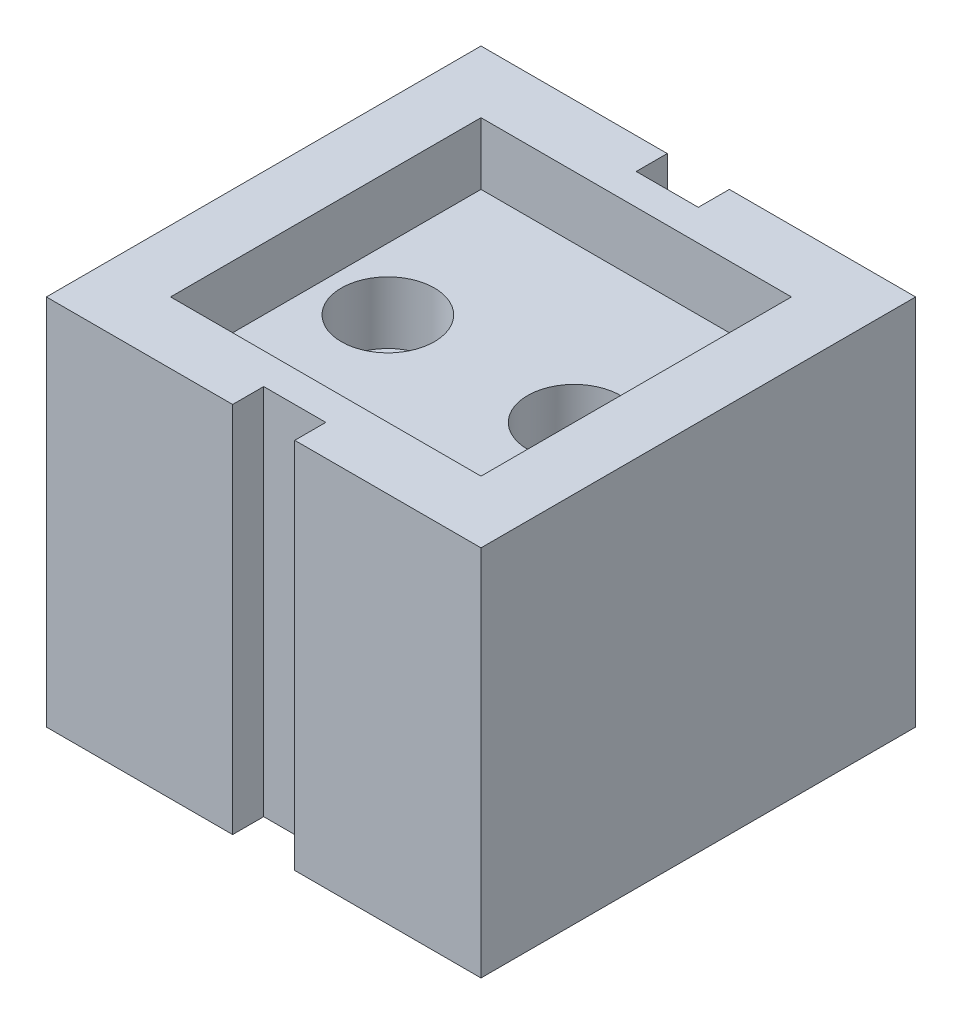
SolidWorks part; units mm, degrees
ref_plane "Front Plane" through (0, 0, 0) normal (0, 0, 1) x (1, 0, 0)
ref_plane "Top Plane" through (0, 0, 0) normal (0, 1, 0) x (1, 0, 0)
ref_plane "Right Plane" through (0, 0, 0) normal (1, 0, 0) x (0, 0, -1)
sketch "Sketch1" plane through (0, 0, 0) normal (0, 1, 0) x (1, 0, 0)
  line L1 (-3.5, -3.5) -> (3.5, -3.5)
  line L2 (-3.5, -3.5) -> (-3.5, 3.5)
  line L3 (-3.5, 3.5) -> (3.5, 3.5)
  line L4 (3.5, -3.5) -> (3.5, 3.5)
  line L5 (-3.5, -3.5) -> (3.5, 3.5) construction
  line L6 (-3.5, 3.5) -> (3.5, -3.5) construction
  point P0 (0, 0)
  dimension "D1" = 7
extrude "Boss-Extrude1" add sketch "Sketch1" along normal blind 6
sketch "Sketch2" plane through (0, 6, 0) normal (0, 1, 0) x (1, 0, 0)
  line L0 (0, 3.5) -> (0, -3.5) construction
  line L1 (3.5, 3.5) -> (-3.5, 3.5) construction
  line L2 (-3.5, -3.5) -> (3.5, -3.5) construction
  line L3 (-3.5, 0) -> (3.5, 0) construction
  line L4 (-3.5, 3.5) -> (-3.5, -3.5) construction
  line L5 (3.5, -3.5) -> (3.5, 3.5) construction
  circle A0 centre (-1.5, 0) radius 0.75
  circle A1 centre (1.5, 0) radius 0.75
  dimension "D1" = 1.5
  dimension "D2" = 3
sketch "Sketch3" plane through (0, 6, 0) normal (0, 1, 0) x (1, 0, 0)
  line L8 (2.5, -2.5) -> (2.5, 2.5)
  line L9 (2.5, 2.5) -> (-2.5, 2.5)
  line L10 (-2.5, 2.5) -> (-2.5, -2.5)
  line L11 (-2.5, -2.5) -> (2.5, -2.5)
  line L12 (2.5, -2.5) -> (2.5, 2.5)
  line L13 (2.5, 2.5) -> (-2.5, 2.5)
  line L14 (-2.5, 2.5) -> (-2.5, -2.5)
  line L15 (-2.5, -2.5) -> (2.5, -2.5)
  dimension "D1" = 1
extrude "Cut-Extrude1" cut sketch "Sketch3" against normal blind 1
extrude "Cut-Extrude2" cut sketch "Sketch2" against normal blind 2
sketch "Sketch4" plane through (0, 6, 0) normal (0, 1, 0) x (1, 0, 0)
  line L0 (0, 3.5) -> (0, -3.5) construction
  line L1 (3.5, 3.5) -> (-3.5, 3.5) construction
  line L2 (-3.5, -3.5) -> (3.5, -3.5) construction
  line L3 (-3.5, 0) -> (3.5, 0) construction
  line L4 (-3.5, 3.5) -> (-3.5, -3.5) construction
  line L5 (3.5, -3.5) -> (3.5, 3.5) construction
  line L6 (-0.5, -4) -> (0.5, -4)
  line L7 (-0.5, 3) -> (0.5, 3)
  line L8 (-0.5, 3) -> (-0.5, 4)
  line L9 (-0.5, 4) -> (0.5, 4)
  line L10 (0.5, 3) -> (0.5, 4)
  line L11 (-0.5, 3) -> (0.5, 4) construction
  line L12 (-0.5, 4) -> (0.5, 3) construction
  line L13 (0.5, -3) -> (0.5, -4)
  line L14 (-0.5, -3) -> (0.5, -3)
  line L15 (-0.5, -3) -> (-0.5, -4)
  dimension "D1" = 1
extrude "Cut-Extrude3" cut sketch "Sketch4" against normal through all
